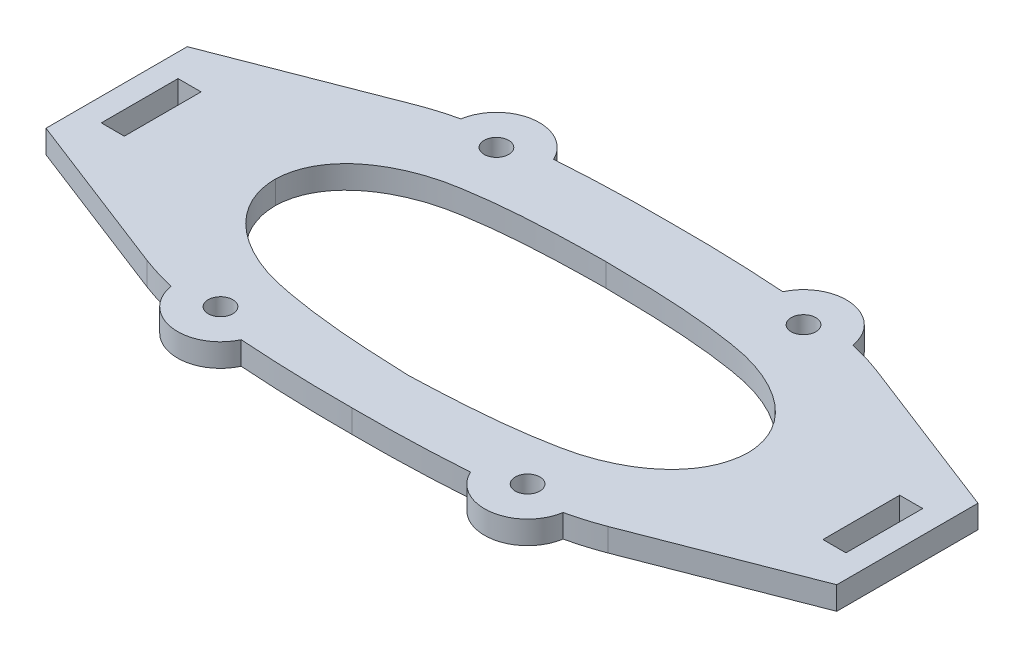
SolidWorks part; units mm, degrees
ref_plane "Plano frontal" through (0, 0, 0) normal (0, 0, 1) x (1, 0, 0)
ref_plane "Plano superior" through (0, 0, 0) normal (0, 1, 0) x (1, 0, 0)
ref_plane "Plano direito" through (0, 0, 0) normal (1, 0, 0) x (0, 0, -1)
ref_plane "Plano1" through (0, 10, 0) normal (0, -1, 0) x (1, 0, 0)
sketch "Esboço1" plane through (0, 10, 0) normal (0, -1, 0) x (1, 0, 0)
  line L0 (-48.5, 5) -> (-45.5, 5)
  line L1 (-45.5, 5) -> (-45.5, -5)
  line L2 (-45.5, -5) -> (-48.5, -5)
  line L3 (-48.5, -5) -> (-48.5, 5)
  line L4 (51.5, -9.1999) -> (30.0128, -17.5235)
  line L5 (51.5, 9.1999) -> (51.5, -9.1999)
  line L6 (30.0128, 17.5235) -> (51.5, 9.1999)
  line L7 (48.5, -5) -> (48.5, 5)
  line L9 (-30.0128, 17.5235) -> (-51.5, 9.1999)
  line L10 (-51.5, 9.1999) -> (-51.5, -9.1999)
  line L11 (-51.5, -9.1999) -> (-30.0128, -17.5235)
  line L14 (0, -20.8143) -> (0, 20.8143) construction
  line L15 (45.5, -5) -> (48.5, -5)
  line L16 (45.5, 5) -> (45.5, -5)
  line L17 (48.5, 5) -> (45.5, 5)
  circle A0 centre (-20, -17.9721) radius 1.6
  arc A1 (0, -20.8143) -> (14.9275, -20.3448) centre (1.3375, 174.1786) ccw
  arc A2 (25.5273, -18.8715) -> (14.9275, -20.3448) centre (20, -17.9721) cw
  circle A3 centre (-20, 17.9721) radius 1.6
  arc A7 (-14.9275, 20.3448) -> (0, 20.8143) centre (-1.2289, -177.6263) cw
  arc A8 (-14.9275, 20.3448) -> (-25.5273, 18.8715) centre (-20, 17.9721) ccw
  arc A9 (-30.0128, 17.5235) -> (-25.5273, 18.8715) centre (-18.4118, -12.9403) cw
  arc A10 (-25.5273, -18.8715) -> (-30.0128, -17.5235) centre (-18.5016, 12.6429) cw
  arc A11 (-25.5273, -18.8715) -> (-14.9275, -20.3448) centre (-20, -17.9721) ccw
  arc A12 (0, -20.8143) -> (-14.9275, -20.3448) centre (-1.3375, 174.1786) cw
  arc A16 (25.5273, -18.8715) -> (30.0128, -17.5235) centre (18.5016, 12.6429) ccw
  arc A17 (30.0128, 17.5235) -> (25.5273, 18.8715) centre (18.4118, -12.9403) ccw
  arc A18 (14.9275, 20.3448) -> (25.5273, 18.8715) centre (20, 17.9721) cw
  arc A19 (14.9275, 20.3448) -> (0, 20.8143) centre (1.2289, -177.6263) ccw
  circle A20 centre (20, 17.9721) radius 1.6
  circle A21 centre (20, -17.9721) radius 1.6
  spline S0 degree 3 poles (0, 13.4818) (-6.2258, 13.2439) (-12.4817, 12.9252) (-24.656, 10.3194) (-30.738, 6.2728) (-30.8333, 0) knots 0 0 0 0 0.5 0.5 1 1 1 1
  spline S1 degree 3 poles (30.8333, 0) (30.6647, -6.1693) (24.4065, -9.8499) (12.3094, -12.0029) (6.143, -12.1444) (0, -12.225) knots 0 0 0 0 0.5 0.5 1 1 1 1
  spline S2 degree 3 poles (0, 13.4818) (6.2258, 13.2439) (12.4817, 12.9252) (24.656, 10.3194) (30.738, 6.2728) (30.8333, 0) knots 0 0 0 0 0.5 0.5 1 1 1 1
  spline S3 degree 3 poles (-30.8333, 0) (-30.6647, -6.1693) (-24.4065, -9.8499) (-12.3094, -12.0029) (-6.143, -12.1444) (0, -12.225) knots 0 0 0 0 0.5 0.5 1 1 1 1
  dimension "D1" = 5.6
  dimension "D2" = 3.2
  dimension "D3" = 194.9975
  dimension "D4" = 32.2881
  dimension "D5" = 23.043
  dimension "D12" = 32.5979
  dimension "D13" = 5.6
  dimension "D14" = 3.2
  dimension "D15" = 198.4444
  dimension "D6" = 18.3998
  dimension "D7" = 23.043
  dimension "D8" = 3
  dimension "D9" = 10
  dimension "D10" = 3
  dimension "D11" = 4.1999
extrude "Ressalto-extrusão1" add sketch "Esboço1" against normal blind 3
